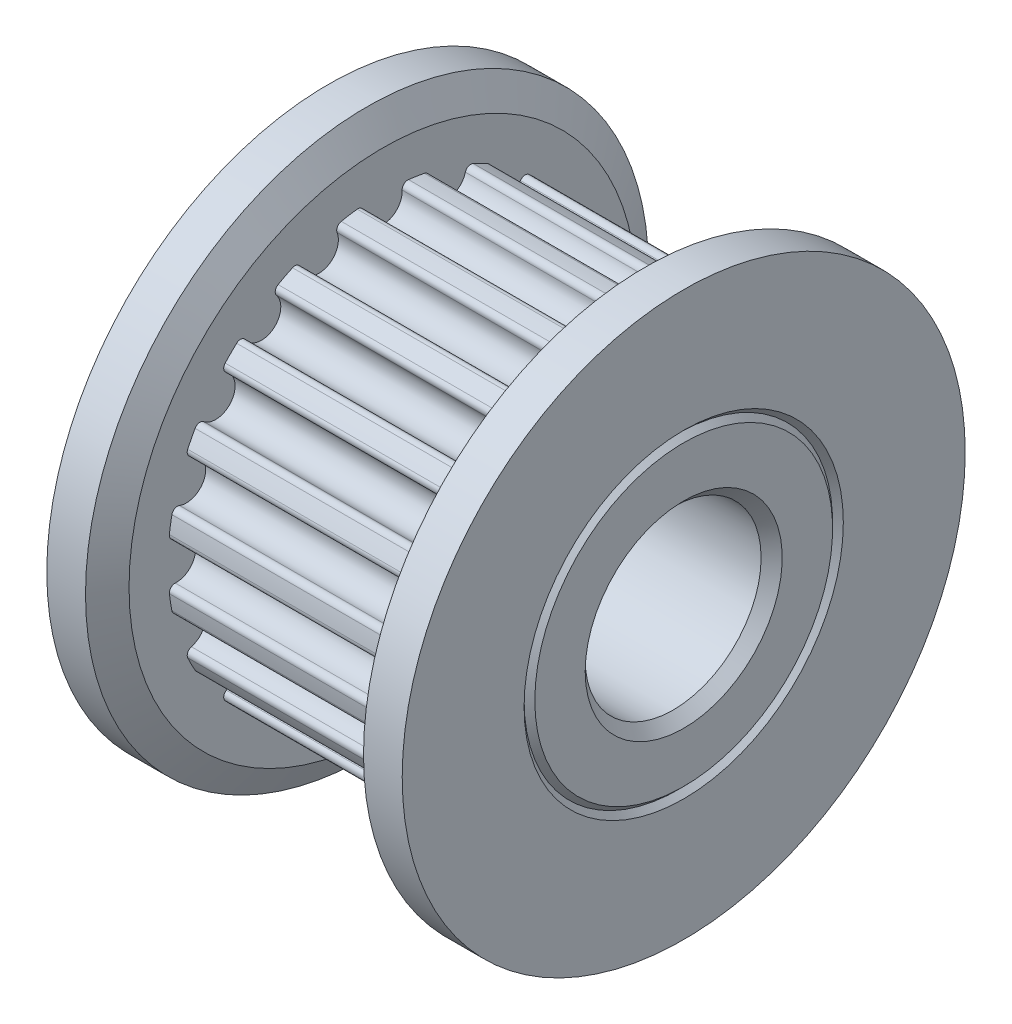
SolidWorks part; units mm, degrees
note: '?' marks a value the reader was unsure of.
other "Main_Body" parameters "D16"=0.5
material "6061-O (SS)"
ref_plane "Сверху" through (0, 0, 0) normal (0, 0, 1) x (1, 0, 0)
ref_plane "Справа" through (0, 0, 0) normal (0, 1, 0) x (1, 0, 0)
ref_plane "Спереди" through (0, 0, 0) normal (1, 0, 0) x (0, 0, -1)
sketch "Эскиз1" plane through (0, 0, 0) normal (0, 0, 1) x (1, 0, 0)
  line L0 (0, 0) -> (0, 7.2132)
  line L1 (0, 7.2132) -> (0.4503, 8)
  line L2 (0.4503, 8) -> (6.9997, 8)
  line L3 (6.9997, 8) -> (7.45, 7.2132)
  line L4 (7.45, 6.11) -> (14.45, 6.11)
  line L5 (14.45, 6.11) -> (14.45, 7.2132)
  line L6 (14.9003, 8) -> (16, 8)
  line L7 (16, 0) -> (16, 4.2314)
  line L8 (16, 4.2314) -> (15.8475, 4.3838)
  line L9 (15.8475, 4.3838) -> (16, 4.5363)
  line L10 (16, 4.5363) -> (16, 8)
  line L11 (0, 0) -> (16, 0)
  line L12 (7.45, 7.2132) -> (7.45, 6.11)
  line L13 (14.45, 7.2132) -> (14.9003, 8)
  dimension "D6" = 6.11
  dimension "D7" = 7.45
  dimension "D8" = 7
  dimension "D10" = 16
  dimension "D11" = 8
revolve "Body" add sketch "Эскиз1" angle 360 about L11
sketch "Эскиз2" plane through (16, 0, 0) normal (1, 0, 0) x (0, 0, -1)
  circle A0 centre (0, 0) radius 2.5
  dimension "D1" = 5
extrude "Bore" cut sketch "Эскиз2" against normal through all
sketch "Эскиз3" plane through (7.45, 0, 0) normal (1, 0, 0) x (0, 0, -1)
  line L0 (0, 0) -> (9.7637, 0) construction
  circle A0 centre (5.5827, -1.8139) radius 0.55
  circle A1 centre (0, 0) radius 6.42 construction
  circle A2 centre (4.7489, -3.4503) radius 0.55
  circle A3 centre (3.4503, -4.7489) radius 0.55
  circle A4 centre (1.8139, -5.5827) radius 0.55
  circle A5 centre (0, -5.87) radius 0.55
  circle A6 centre (5.87, 0) radius 0.55
  circle A7 centre (-1.8139, -5.5827) radius 0.55
  circle A8 centre (-3.4503, -4.7489) radius 0.55
  circle A9 centre (-4.7489, -3.4503) radius 0.55
  circle A10 centre (-5.5827, -1.8139) radius 0.55
  circle A11 centre (-5.87, 0) radius 0.55
  circle A12 centre (-5.5827, 1.8139) radius 0.55
  circle A13 centre (-4.7489, 3.4503) radius 0.55
  circle A14 centre (-3.4503, 4.7489) radius 0.55
  circle A17 centre (-1.8139, 5.5827) radius 0.55
  circle A18 centre (0, 5.87) radius 0.55
  circle A19 centre (1.8139, 5.5827) radius 0.55
  circle A20 centre (3.4503, 4.7489) radius 0.55
  circle A21 centre (4.7489, 3.4503) radius 0.55
  circle A22 centre (5.5827, 1.8139) radius 0.55
  point P45 (0, 0)
  dimension "D1" = 12.84
  dimension "D2" = 20
  dimension "D3" = 1.1
extrude "20T" cut sketch "Эскиз3" along normal blind 7
fillet "Fillet" radius 0.16 40 edges at (10.95, 0.5045, -6.0891) (10.95, -0.5045, -6.0891) (10.95, -1.4019, -5.947) (10.95, -2.3614, -5.6352) (10.95, -3.171, -5.2227) (10.95, -3.9872, -4.6297) (10.95, -4.6297, -3.9872) (10.95, -5.2227, -3.171) (10.95, -5.6352, -2.3614) (10.95, -5.947, -1.4019) (10.95, -6.0891, -0.5045) (10.95, -6.0891, 0.5045) (10.95, -5.947, 1.4019) (10.95, -5.6352, 2.3614) (10.95, -5.2227, 3.171) (10.95, -4.6297, 3.9872) (10.95, -3.9872, 4.6297) (10.95, -3.171, 5.2227) (10.95, -2.3614, 5.6352) (10.95, -1.4019, 5.947) (10.95, -0.5045, 6.0891) (10.95, 0.5045, 6.0891) (10.95, 1.4019, 5.947) (10.95, 2.3614, 5.6352) (10.95, 3.171, 5.2227) (10.95, 3.9872, 4.6297) (10.95, 4.6297, 3.9872) (10.95, 5.2227, 3.171) (10.95, 5.6352, 2.3614) (10.95, 5.947, 1.4019) (10.95, 6.0891, 0.5045) (10.95, 6.0891, -0.5045) (10.95, 5.947, -1.4019) (10.95, 5.6352, -2.3614) (10.95, 5.2227, -3.171) (10.95, 4.6297, -3.9872) (10.95, 3.9872, -4.6297) (10.95, 3.171, -5.2227) (10.95, 2.3614, -5.6352) (10.95, 1.4019, -5.947)
ref_axis "Axis1" through (0, 0, 0) along (1, 0, 0)?
chamfer "Chamfer2" distance 0.3 angle 45 1 edges at (16, 0, -2.5)
sketch "Sketch2" plane through (0, 0, 0) normal (0, 1, 0) x (1, 0, 0)
  line L0 (6.9997, 8) -> (5.8997, 8) construction
  line L2 (5.8997, 8) -> (-0.6199, 8)
  line L3 (5.8997, 8) -> (5.8997, -8.1343)
  line L4 (5.8997, -8.1343) -> (-0.6199, -8.1343)
  line L5 (-0.6199, 8) -> (-0.6199, -8.1343)
  dimension "D1" = 1.1
extrude "Cut-Extrude1" cut sketch "Sketch2" against normal mid plane 20
